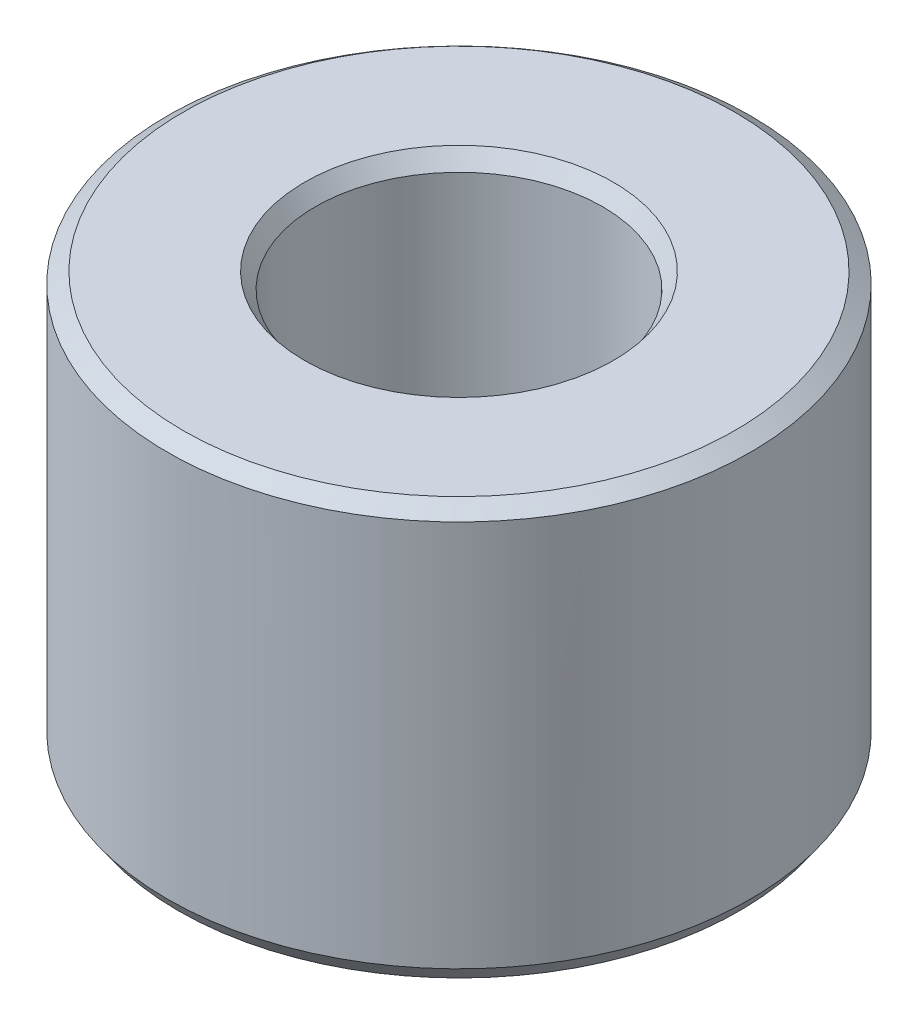
SolidWorks part; units mm, degrees
ref_plane "Front Plane" through (0, 0, 0) normal (0, 0, 1) x (1, 0, 0)
ref_plane "Top Plane" through (0, 0, 0) normal (0, 1, 0) x (1, 0, 0)
ref_plane "Right Plane" through (0, 0, 0) normal (1, 0, 0) x (0, 0, -1)
sketch "Sketch1" plane through (0, 0, 0) normal (0, 1, 0) x (1, 0, 0)
  circle A0 centre (0, 0) radius 37.5
  dimension "SLEEVE_OD" = 75
extrude "Boss-Extrude1" add sketch "Sketch1" along normal blind 53.206
sketch "Sketch2" plane through (0, 0, 0) normal (0, 1, 0) x (1, 0, 0)
  circle A0 centre (0, 0) radius 18.4636
  dimension "BORE_D" = 36.9272
extrude "Cut-Extrude1" cut sketch "Sketch2" along normal through all
chamfer "Chamfer1" distance 1.4074 angle 55.057 4 edges at (0, 53.206, 18.4636) (0, 0, 18.4636) (0, 0, 37.5) (0, 53.206, 37.5) first distance on face at (0, 53.206, 18.4636) first distance on face at (0, 0, 18.4636) first distance on face at (0, 53.206, 37.5)
